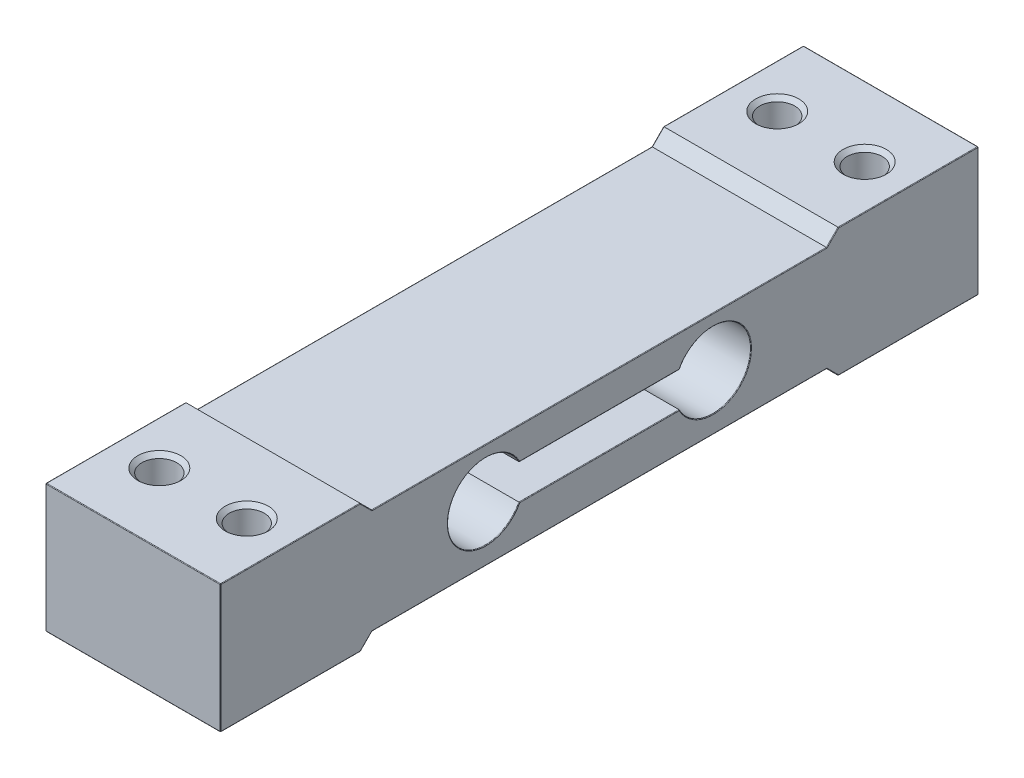
SolidWorks part; units mm, degrees
ref_plane "Front Plane" through (0, 0, 0) normal (0, 0, 1) x (1, 0, 0)
ref_plane "Top Plane" through (0, 0, 0) normal (0, 1, 0) x (1, 0, 0)
ref_plane "Right Plane" through (0, 0, 0) normal (1, 0, 0) x (0, 0, -1)
sketch "Эскиз1" plane through (0, 0, 0) normal (1, 0, 0) x (0, 0, -1)
  line L0 (24, 22) -> (26, 20)
  line L1 (106, 0) -> (130, 0)
  line L2 (0, 0) -> (0, 22)
  line L3 (0, 22) -> (24, 22)
  line L4 (130, 0) -> (130, 22)
  line L5 (26, 20) -> (104, 20)
  line L6 (104, 20) -> (106, 22)
  line L7 (106, 22) -> (130, 22)
  line L8 (0, 11) -> (143.2604, 11) construction
  line L9 (104, 2) -> (106, 0)
  line L10 (26, 2) -> (104, 2)
  line L11 (0, 0) -> (24, 0)
  line L12 (24, 0) -> (26, 2)
  point P14 (130, 11)
  dimension "D3" = 24
  dimension "D4" = 24
  dimension "D5" = 45
  dimension "D6" = 45
  dimension "D7" = 2
extrude "Бобышка-Вытянуть1" add sketch "Эскиз1" along normal blind 15 and the other way blind 15
sketch "Эскиз2" plane through (15, 0, 0) normal (1, 0, 0) x (0, 0, -1)
  line L0 (91, -11.6364) -> (91, 32.8489) construction
  line L1 (39, 31.9285) -> (39, -14.2442) construction
  line L2 (51.2663, 14.5266) -> (78.7337, 14.5266)
  line L3 (45.5, 11.5266) -> (84.5, 11.5266) construction
  line L4 (51.2663, 8.5266) -> (78.7337, 8.5266)
  arc A0 (78.7337, 8.5266) -> (78.7337, 14.5266) centre (84.5, 11.5266) ccw
  arc A1 (51.2663, 14.5266) -> (51.2663, 8.5266) centre (45.5, 11.5266) ccw
  dimension "D1" = 15
  dimension "D4" = 13
  dimension "D2" = 15
  dimension "D3" = 3
extrude "Вырез-Вытянуть1" cut sketch "Эскиз2" against normal blind 45
sketch "Эскиз12" plane through (0, 0, 0) normal (0, -1, 0) x (1, 0, 0)
  line L0 (-15, -130) -> (15, -130) construction
  line L1 (7.5, -118) -> (-7.5, -118) construction
  line L2 (-7.5, -118) -> (-7.5, -12) construction
  line L3 (-7.5, -12) -> (7.5, -12) construction
  line L4 (7.5, -12) -> (7.5, -118) construction
  circle A0 centre (7.5, -118) radius 3
  circle A1 centre (-7.5, -118) radius 3
  circle A2 centre (7.5, -12) radius 3
  circle A3 centre (-7.5, -12) radius 3
  point P14 (-6.2109, -118.4365)
  dimension "D1" = 12
  dimension "D2" = 106
  dimension "D3" = 15
  dimension "D5" = 6
extrude "Вырез-Вытянуть2" cut sketch "Эскиз12" against normal blind 40
chamfer "Фаска1" distance 0.7 angle 45 8 edges at (-7.5, 0, -121) (-7.5, 22, -115) (7.5, 0, -121) (7.5, 22, -115) (7.5, 0, -15) (7.5, 22, -9) (-7.5, 0, -15) (-7.5, 22, -9)
fillet "Скругление1" radius 0.1 36 edges at (-15, 0, -118) (-15, 22, -118) (-15, 21, -105) (-15, 20, -65) (-15, 21, -25) (-15, 22, -12) (-15, 0, -12) (-15, 1, -25) (-15, 2, -65) (-15, 1, -105) (-15, 11.5266, -39) (-15, 14.5266, -65) (-15, 11.5266, -91) (-15, 8.5266, -65) (-15, 11, -130) (0, 0, -130) (0, 22, -130) (-15, 11, 0) (0, 22, 0) (0, 0, 0) (15, 2, -65) (15, 1, -25) (15, 0, -12) (15, 11, 0) (15, 22, -12) (15, 21, -25) (15, 20, -65) (15, 21, -105) (15, 22, -118) (15, 11, -130) (15, 0, -118) (15, 1, -105) (15, 14.5266, -65) (15, 11.5266, -39) (15, 8.5266, -65) (15, 11.5266, -91)
sketch "Эскиз13" plane through (-15, 0, 0) normal (-1, 0, 0) x (0, 0, 1)
  line L0 (-129.9, 21.9) -> (-129.9, 0.1) construction
  line L1 (-129.9, 22) -> (-106, 22) construction
  circle A0 centre (-123.9, 11) radius 1.75
  point P4 (-129.9, 11)
  dimension "D1" = 3.5
  dimension "D2" = 6
  dimension "D3" = 11
extrude "Вырез-Вытянуть3" cut sketch "Эскиз13" against normal blind 10
sketch "Эскиз15" plane through (-5, 0, 0) normal (-1, 0, 0) x (0, 0, 1)
  circle A0 centre (-123.9, 11) radius 1.75
extrude "Бобышка-Вытянуть2" add sketch "Эскиз15" along normal blind 15 separate body
